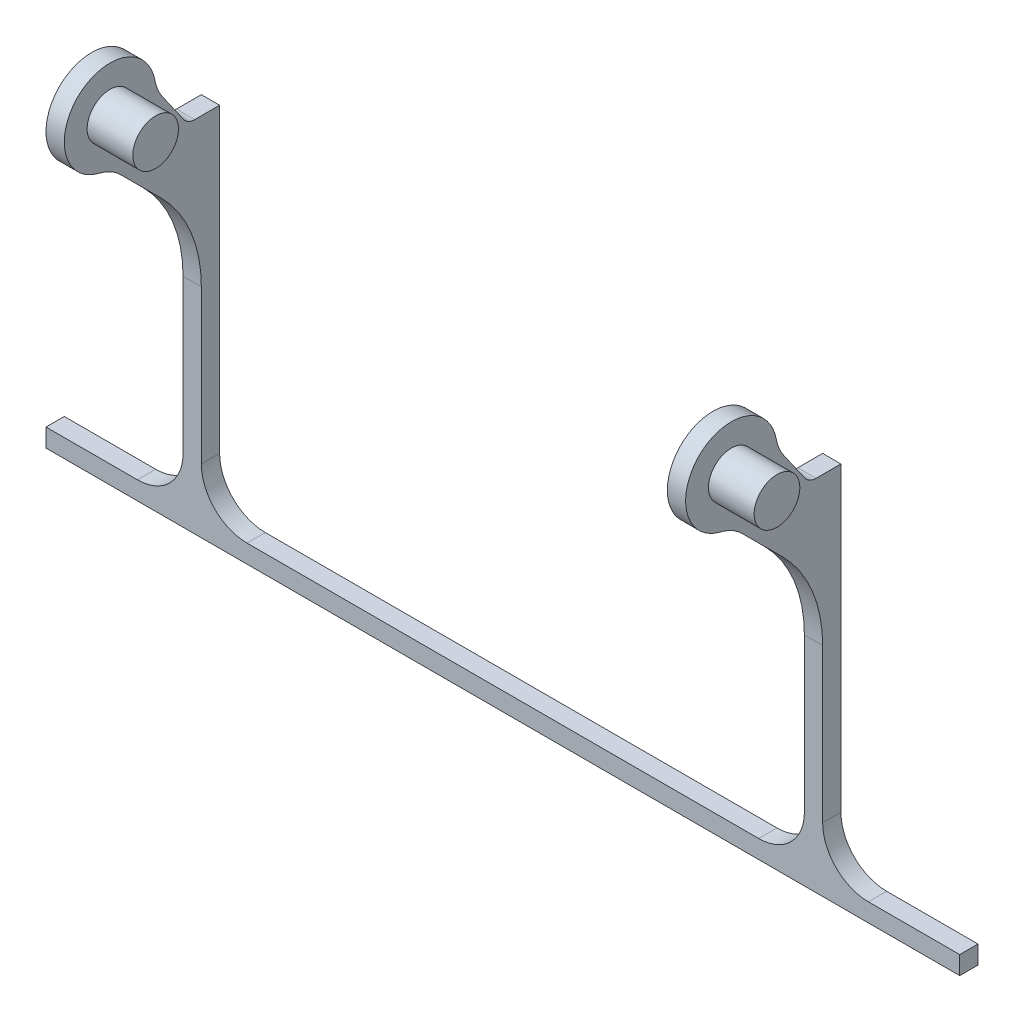
SolidWorks part; units mm, degrees
ref_plane "Plan de face" through (0, 0, 0) normal (0, 0, 1) x (1, 0, 0)
ref_plane "Plan de dessus" through (0, 0, 0) normal (0, 1, 0) x (1, 0, 0)
ref_plane "Plan de droite" through (0, 0, 0) normal (1, 0, 0) x (0, 0, -1)
sketch "Esquisse1" plane through (0, 0, 0) normal (0, 0, 1) x (1, 0, 0)
  line L0 (-100, -100) -> (100, -100) construction
  line L1 (100, -100) -> (100, -180) construction
  line L2 (100, -180) -> (-100, -180) construction
  line L3 (-100, -180) -> (-100, -100) construction
  line L4 (-100, -180) -> (-100, -176) construction
  line L5 (-100, -176) -> (-70, -176) construction
  line L6 (-70, -176) -> (-70, -100) construction
  line L7 (-70, -100) -> (-66, -100) construction
  line L8 (-66, -100) -> (-66, -176) construction
  line L9 (-66, -176) -> (66, -176) construction
  line L10 (66, -176) -> (66, -100) construction
  line L11 (66, -100) -> (70, -100) construction
  line L12 (70, -100) -> (70, -176) construction
  line L13 (70, -176) -> (100, -176) construction
  line L14 (-100, -97.7507) -> (-100, -110) construction
  line L15 (-100, 100) -> (-100, -100) construction
  line L16 (-100, -110) -> (-70, -110) construction
  line L17 (-70, -110) -> (-66, -110) construction
  line L18 (-66, -110) -> (66, -110) construction
  line L19 (66, -110) -> (70, -110) construction
  line L20 (70, -110) -> (100, -110) construction
  line L21 (-70, -110) -> (-66, -110)
  line L22 (-66, -110) -> (-66, -176)
  line L23 (-66, -176) -> (66, -176)
  line L24 (66, -176) -> (66, -110)
  line L25 (66, -110) -> (70, -110)
  line L26 (70, -110) -> (70, -176)
  line L27 (70, -176) -> (100, -176)
  line L28 (100, -176) -> (100, -180)
  line L29 (100, -180) -> (-100, -180)
  line L30 (-100, -180) -> (-100, -176)
  line L31 (-100, -176) -> (-70, -176)
  line L32 (-70, -176) -> (-70, -110)
  dimension "D1" = 4
  dimension "D2" = 4
  dimension "D3" = 4
  dimension "D4" = 4
  dimension "D5" = 4
  dimension "D6" = 30
  dimension "D7" = 30
  dimension "D8" = 10
  dimension "D9" = 80
extrude "Boss.-Extru.1" add sketch "Esquisse1" against normal blind 4
sketch "Esquisse2" plane through (70, 0, 0) normal (1, 0, 0) x (0, 0, -1)
  line L0 (0, -110) -> (-20, -110) construction
  line L1 (-20, -110) -> (-20, -90) construction
  line L2 (4, -110) -> (-10, -90) construction
  line L3 (0, -110) -> (0, -120) construction
  line L4 (0, -176) -> (0, -110) construction
  line L5 (0, -120) -> (-20, -100) construction
  line L6 (0, -120) -> (-20, -100)
  line L7 (4, -110) -> (-10, -90)
  line L8 (0, -120) -> (0, -110)
  line L9 (0, -110) -> (4, -110)
  arc A0 (-10, -90) -> (-20, -100) centre (-20, -90) ccw
  dimension "D3" = 20
  dimension "D1" = 20
  dimension "D2" = 20
  dimension "D4" = 10
extrude "Boss.-Extru.2" add sketch "Esquisse2" against normal blind 4
sketch "Esquisse3" plane through (-70, 0, 0) normal (-1, 0, 0) x (0, 0, 1)
  line L0 (-4, -110) -> (10, -90) construction
  line L1 (20, -100) -> (0, -120) construction
  line L2 (-4, -110) -> (10, -90)
  line L3 (20, -100) -> (0, -120)
  line L4 (-4, -110) -> (0, -110)
  line L5 (0, -110) -> (0, -120)
  arc A0 (20, -100) -> (10, -90) centre (20, -90) ccw construction
  arc A1 (20, -100) -> (10, -90) centre (20, -90) ccw
extrude "Boss.-Extru.3" add sketch "Esquisse3" against normal blind 4
fillet "Congé1" radius 30 2 edges at (68, -120, 0) (-68, -120, 0)
fillet "Congé2" radius 30 2 edges at (-68, -110, -4) (68, -110, -4)
fillet "Congé3" radius 10 4 edges at (66, -176, -2) (-66, -176, -2) (-70, -176, -2) (70, -176, -2)
sketch "Esquisse4" plane through (-70, 0, 0) normal (-1, 0, 0) x (0, 0, 1)
  line L0 (-4, -119.4567) -> (-4, -100)
  line L1 (-4, -100) -> (3, -100)
  line L2 (10, -90) -> (1.423, -102.2528) construction
  line L3 (3, -100) -> (-4, -119.4567)
extrude "Boss.-Extru.4" add sketch "Esquisse4" against normal blind 4
ref_plane "Plan1" through (-66, -100, 3) normal (0, 0, -1) x (-1, 0, 0)
sketch "Esquisse6" plane through (70, 0, 0) normal (1, 0, 0) x (0, 0, -1)
  line L0 (4, -119.4567) -> (4, -100)
  line L1 (4, -100) -> (-3, -100)
  line L2 (-3, -100) -> (4, -119.4567)
extrude "Boss.-Extru.5" add sketch "Esquisse6" against normal blind 4
sketch "Esquisse7" plane through (70, 0, 0) normal (1, 0, 0) x (0, 0, -1)
  line L0 (4, -100) -> (-20, -100) construction
  line L1 (-20, -100) -> (-20, -90) construction
  circle A0 centre (-20, -90) radius 5
  dimension "D1" = 10
extrude "Boss.-Extru.6" add sketch "Esquisse7" along normal blind 10
sketch "Esquisse9" plane through (-70, 0, 0) normal (-1, 0, 0) x (0, 0, 1)
  line L0 (-4, -100) -> (20, -100) construction
  line L1 (20, -100) -> (20, -90) construction
  circle A0 centre (20, -90) radius 5
  dimension "D1" = 10
extrude "Boss.-Extru.7" add sketch "Esquisse9" against normal blind 14
fillet "Congé4" radius 10 4 edges at (-68, -100, 20) (-68, -90, 10) (68, -90, 10) (68, -100, 20)
fillet "Congé5" radius 3 2 edges at (-68, -100, 3) (68, -100, 3)
